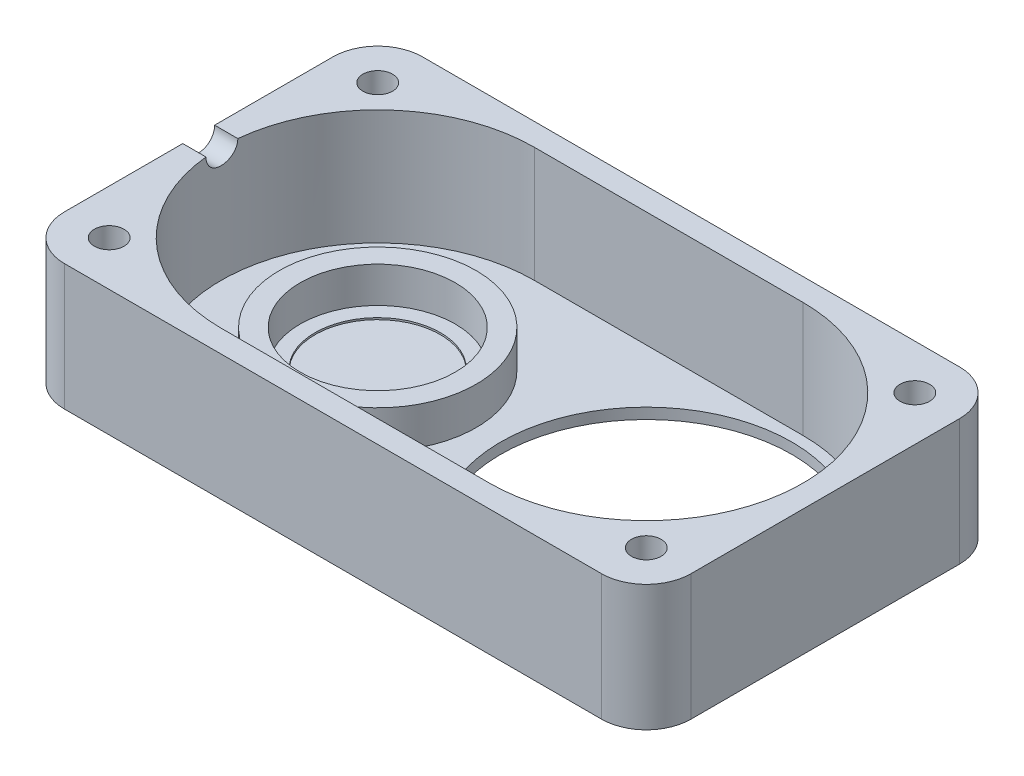
SolidWorks part; units mm, degrees
ref_plane "Front Plane" through (0, 0, 0) normal (0, 0, 1) x (1, 0, 0)
ref_plane "Top Plane" through (0, 0, 0) normal (0, 1, 0) x (1, 0, 0)
ref_plane "Right Plane" through (0, 0, 0) normal (1, 0, 0) x (0, 0, -1)
sketch "Sketch1" plane through (0, 0, 0) normal (0, 1, 0) x (1, 0, 0)
  line L0 (38.1, 19.05) -> (38.1, 25.4) construction
  line L1 (-19.05, -25.4) -> (57.15, -25.4)
  line L2 (-25.4, -19.05) -> (-25.4, 19.05)
  line L3 (-19.05, 25.4) -> (57.15, 25.4)
  line L4 (63.5, -19.05) -> (63.5, 19.05)
  line L5 (-25.4, -25.4) -> (63.5, 25.4) construction
  line L6 (-25.4, 25.4) -> (63.5, -25.4) construction
  line L7 (57.15, 0) -> (63.5, 0) construction
  line L9 (-7.62, -11.176) -> (7.62, -11.176) construction
  line L10 (-7.62, -11.176) -> (-7.62, 11.176) construction
  line L11 (-7.62, 11.176) -> (7.62, 11.176) construction
  line L12 (7.62, -11.176) -> (7.62, 11.176) construction
  line L13 (-7.62, -11.176) -> (7.62, 11.176) construction
  line L14 (-7.62, 11.176) -> (7.62, -11.176) construction
  circle A0 centre (0, 0) radius 19.05 construction
  circle A1 centre (38.1, 0) radius 19.05 construction
  circle A2 centre (38.1, 0) radius 12.7 construction
  circle A3 centre (38.1, 0) radius 20.6375
  arc A4 (-25.4, 19.05) -> (-19.05, 25.4) centre (-19.05, 19.05) cw
  arc A5 (-19.05, -25.4) -> (-25.4, -19.05) centre (-19.05, -19.05) cw
  arc A6 (57.15, -25.4) -> (63.5, -19.05) centre (57.15, -19.05) ccw
  arc A7 (57.15, 25.4) -> (63.5, 19.05) centre (57.15, 19.05) cw
  circle A8 centre (-19.05, 19.05) radius 2.1
  circle A9 centre (-19.05, -19.05) radius 2.1
  circle A10 centre (57.15, -19.05) radius 2.1
  circle A11 centre (57.15, 19.05) radius 2.1
  point P6 (19.05, 0)
  dimension "D1" = 38.1
  dimension "D2" = 38.1
  dimension "D3" = 50.8
  dimension "D7" = 25.4
  dimension "D8" = 41.275
  dimension "D9" = 6.35
  dimension "D10" = 4.2
  dimension "D4" = 88.9
  dimension "D5" = 15.24
  dimension "D6" = 22.352
extrude "Boss-Extrude1" add sketch "Sketch1" along normal blind 17.8791
sketch "Sketch2" plane through (0, 17.8791, 0) normal (0, 1, 0) x (1, 0, 0)
  line L0 (0, 22.225) -> (38.1, 22.225)
  line L1 (38.1, -22.225) -> (0, -22.225)
  arc A0 (0, 22.225) -> (0, -22.225) centre (0, 0) ccw
  arc A1 (38.1, -22.225) -> (38.1, 22.225) centre (38.1, 0) ccw
  dimension "D1" = 44.45
extrude "Cut-Extrude1" cut sketch "Sketch2" against normal offset from surface (16.3551 mm away) 1.524 up to face at (57.15, 0, 21.15)
sketch "Sketch3" plane through (0, 1.524, 0) normal (0, 1, 0) x (1, 0, 0)
  circle A0 centre (0, 0) radius 13.97
  circle A1 centre (0, 0) radius 8.89
  dimension "D1" = 27.94
  dimension "D2" = 17.78
extrude "Boss-Extrude2" add sketch "Sketch3" along normal blind 0.254
sketch "Sketch4" plane through (0, 1.778, 0) normal (0, 1, 0) x (1, 0, 0)
  circle A0 centre (0, 0) radius 10.9995
  circle A1 centre (0, 0) radius 13.97 construction
  circle A2 centre (0, 0) radius 13.97
  dimension "D1" = 21.9989
extrude "Boss-Extrude3" add sketch "Sketch4" along normal blind 5.08
sketch "Sketch6" plane through (-25.4, 0, 0) normal (-1, 0, 0) x (0, 0, 1)
  line L0 (-19.05, 17.8791) -> (19.05, 17.8791) construction
  circle A0 centre (0, 17.8791) radius 2.2606
  dimension "D1" = 4.5212
extrude "Cut-Extrude2" cut sketch "Sketch6" against normal up to next
sketch "Sketch7" plane through (0, 0, 0) normal (0, -1, 0) x (1, 0, 0)
  circle A0 centre (-19.05, 19.05) radius 3.75
  circle A1 centre (-19.05, -19.05) radius 3.75
  circle A2 centre (57.15, -19.05) radius 3.75
  circle A3 centre (57.15, 19.05) radius 3.75
  dimension "D1" = 7.5
extrude "Cut-Extrude3" cut sketch "Sketch7" against normal blind 4.5
sketch "Sketch8" plane through (0, 0, 0) normal (0, -1, 0) x (1, 0, 0)
  line L0 (20.4837, 10.7504) -> (14.9909, 15.9577)
  line L1 (14.9909, 15.9577) -> (20.9323, 22.225)
  line L2 (20.9323, 22.225) -> (26.4252, 17.0178)
  line L3 (17.9616, 19.0913) -> (38.1, 0) construction
  line L4 (0, 22.225) -> (38.1, 22.225) construction
  circle A0 centre (38.1, 0) radius 20.6375 construction
  arc A1 (26.4252, 17.0178) -> (20.4837, 10.7504) centre (38.1, 0) ccw
  point P8 (23.1229, 14.1984)
  point P9 (13.4342, 18.4413)
  point P10 (13.0836, 17.9629)
  point P11 (0, 0)
  dimension "D1" = 8.636
  dimension "D2" = 7.112
extrude "Cut-Extrude4" cut sketch "Sketch8" against normal through all
